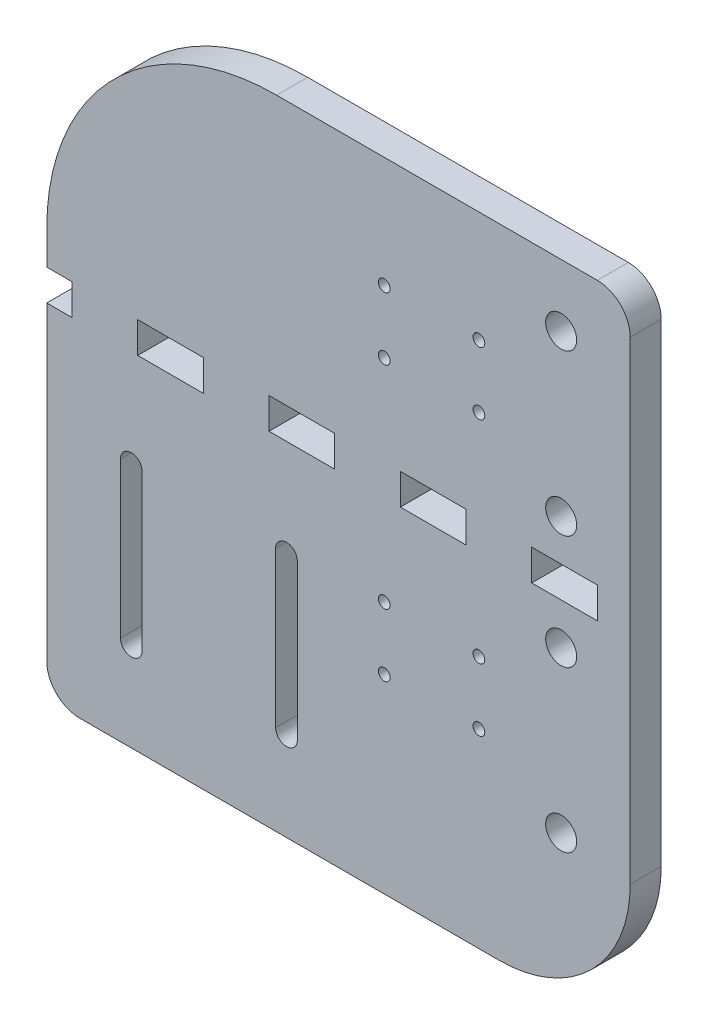
SolidWorks part; units mm, degrees
ref_plane "Front Plane" through (0, 0, 0) normal (0, 0, 1) x (1, 0, 0)
ref_plane "Top Plane" through (0, 0, 0) normal (0, 1, 0) x (1, 0, 0)
ref_plane "Right Plane" through (0, 0, 0) normal (1, 0, 0) x (0, 0, -1)
sketch "Sketch1" plane through (0, 0, 0) normal (0, 0, 1) x (-1, 0, 0)
  line L0 (5.4449, 19.1182) -> (-12.8627, 19.1182) construction
  line L1 (-15.4204, 35.8131) -> (8.0026, 35.8131) construction
  line L2 (-15.4204, 35.8131) -> (-15.4204, 14.5439) construction
  line L3 (-15.4204, 14.5439) -> (8.0026, 14.5439) construction
  line L4 (8.0026, 35.8131) -> (8.0026, 14.5439) construction
  line L5 (5.4449, 19.1182) -> (5.4449, 31.2335) construction
  line L6 (5.4449, 31.2335) -> (-12.8627, 31.2335) construction
  line L7 (-12.8627, 31.2335) -> (-12.8627, 19.1182) construction
  line L8 (-15.4204, 14.5439) -> (-15.4204, -17.2061) construction
  line L9 (-35.7704, 4.6785) -> (-35.7704, 45.6785) construction
  line L10 (-35.7704, 45.6785) -> (-21.7704, 45.6785) construction
  line L11 (-21.7704, 45.6785) -> (-21.7704, 4.6785) construction
  line L12 (-21.7704, 4.6785) -> (-35.7704, 4.6785) construction
  line L13 (-1015.4204, -1.3311) -> (48984.5796, -1.3311) construction
  line L14 (-15.4204, 25.1785) -> (-21.7704, 25.1785)
  line L15 (-21.7704, -7.3406) -> (-35.7704, -7.3406) construction
  line L16 (-21.7704, -48.3406) -> (-21.7704, -7.3406) construction
  line L17 (-35.7704, -48.3406) -> (-21.7704, -48.3406) construction
  line L18 (-35.7704, -7.3406) -> (-35.7704, -48.3406) construction
  line L19 (-12.8627, -33.8956) -> (-12.8627, -21.7803) construction
  line L20 (5.4449, -33.8956) -> (-12.8627, -33.8956) construction
  line L21 (5.4449, -21.7803) -> (5.4449, -33.8956) construction
  line L22 (8.0026, -38.4752) -> (8.0026, -17.2061) construction
  line L23 (-15.4204, -17.2061) -> (8.0026, -17.2061) construction
  line L24 (-15.4204, -38.4752) -> (-15.4204, -17.2061) construction
  line L25 (-15.4204, -38.4752) -> (8.0026, -38.4752) construction
  line L26 (5.4449, -21.7803) -> (-12.8627, -21.7803) construction
  line L27 (-15.4204, -27.8406) -> (-21.7704, -27.8406)
  line L28 (-15.4204, -1.3311) -> (-15.4204, 8.6689) construction
  line L29 (39.3526, 8.6689) -> (39.3526, 61.6689) construction
  line L30 (70.7026, -4.3283) -> (70.7026, -10.9042)
  line L31 (14.3526, 8.6689) -> (14.3526, 61.6689) construction
  line L32 (14.3526, 61.6689) -> (64.3526, 61.6689) construction
  line L33 (64.3526, 61.6689) -> (64.3526, 8.6689) construction
  line L34 (64.3526, 8.6689) -> (14.3526, 8.6689) construction
  line L35 (24.3526, 50.6689) -> (24.3526, 20.6689) construction
  line L36 (24.3526, 61.6689) -> (24.3526, 50.6689) construction
  line L37 (24.3526, 20.6689) -> (24.3526, 50.6689) construction
  line L38 (22.2526, 20.6689) -> (22.2526, 50.6689)
  line L39 (26.4526, 20.6689) -> (26.4526, 50.6689)
  line L40 (54.3526, 50.6689) -> (54.3526, 20.6689) construction
  line L41 (54.3526, 20.6689) -> (54.3526, 50.6689) construction
  line L42 (56.4526, 20.6689) -> (56.4526, 50.6689)
  line L43 (52.2526, 20.6689) -> (52.2526, 50.6689)
  line L44 (-35.7704, -4.3283) -> (-35.7704, 1.6661)
  line L45 (-35.7704, 1.6661) -> (-23.0704, 1.6661)
  line L46 (-23.0704, 1.6661) -> (-23.0704, -4.3283)
  line L48 (-10.3704, -4.3283) -> (-10.3704, 1.6661)
  line L49 (64.3526, 68.0189) -> (-16.7204, 68.0189)
  line L50 (70.7026, 61.6689) -> (70.7026, 1.6661)
  line L51 (26.2526, -55.3542) -> (-35.7704, -55.3542)
  line L52 (-42.1204, 42.6189) -> (-42.1204, -49.0042)
  line L53 (-10.3704, 1.6661) -> (2.3296, 1.6661)
  line L54 (2.3296, 1.6661) -> (2.3296, -4.3283)
  line L56 (15.0296, -4.3283) -> (15.0296, 1.6661)
  line L57 (15.0296, 1.6661) -> (27.7296, 1.6661)
  line L58 (27.7296, 1.6661) -> (27.7296, -4.3283)
  line L60 (40.4296, -4.3283) -> (40.4296, 1.6661)
  line L61 (40.4296, 1.6661) -> (53.1296, 1.6661)
  line L62 (53.1296, 1.6661) -> (53.1296, -4.3283)
  line L64 (65.8296, -4.3283) -> (65.8296, 1.6661)
  line L65 (65.8296, 1.6661) -> (70.7026, 1.6661)
  line L66 (65.8296, -4.3283) -> (70.7026, -4.3283)
  line L67 (40.4296, -4.3283) -> (53.1296, -4.3283)
  line L68 (15.0296, -4.3283) -> (27.7296, -4.3283)
  line L69 (-10.3704, -4.3283) -> (2.3296, -4.3283)
  line L70 (-35.7704, -4.3283) -> (-23.0704, -4.3283)
  circle A0 centre (-12.8627, 31.2335) radius 1.1321
  circle A1 centre (5.4449, 31.2335) radius 1.1321
  circle A2 centre (5.4449, 19.1182) radius 1.1321
  circle A3 centre (-12.8627, 19.1182) radius 1.1321
  circle A4 centre (-28.7704, -43.3406) radius 3
  circle A5 centre (-28.7704, -12.3406) radius 3
  circle A6 centre (-12.8627, -21.7803) radius 1.1321
  circle A7 centre (5.4449, -21.7803) radius 1.1321
  circle A8 centre (-28.7704, 9.6785) radius 3
  circle A9 centre (-28.7704, 40.6785) radius 3
  circle A10 centre (5.4449, -33.8956) radius 1.1321
  circle A11 centre (-12.8627, -33.8956) radius 1.1321
  arc A12 (22.2526, 20.6689) -> (26.4526, 20.6689) centre (24.3526, 20.6689) ccw
  arc A13 (26.4526, 50.6689) -> (22.2526, 50.6689) centre (24.3526, 50.6689) ccw
  arc A14 (56.4526, 20.6689) -> (52.2526, 20.6689) centre (54.3526, 20.6689) cw
  arc A15 (52.2526, 50.6689) -> (56.4526, 50.6689) centre (54.3526, 50.6689) cw
  arc A16 (26.2526, -55.3542) -> (70.7026, -10.9042) centre (26.2526, -10.9042) ccw
  arc A17 (-16.7204, 68.0189) -> (-42.1204, 42.6189) centre (-16.7204, 42.6189) ccw
  arc A18 (64.3526, 68.0189) -> (70.7026, 61.6689) centre (64.3526, 61.6689) cw
  arc A19 (-35.7704, -55.3542) -> (-42.1204, -49.0042) centre (-35.7704, -49.0042) cw
  point P42 (-15.4204, -1.3311)
  point P57 (24.3526, 35.6689)
  point P66 (54.3526, 35.6689)
  dimension "D8" = 44.45
  dimension "D9" = 25.4
  dimension "D10" = 6.35
  dimension "D11" = 6.35
  dimension "D1" = 21.2692
  dimension "D2" = 23.423
  dimension "D3" = 4.5742
  dimension "D4" = 2.5577
  dimension "D5" = 31.75
  dimension "D6" = 30
  dimension "D7" = 11
  dimension "D12" = 4
extrude "Boss-Extrude1" add sketch "Sketch1" along normal blind 5.9944 contours A19 L51 L50 A18 L49 A17 L52 A13 L39 A12 L38 A10 A9 A8 A6 A4 A3 A2 A1 A0 A5 A7 A11 L43 A15 L42 A14 region at (-13.1694, -7.0999, 0)
